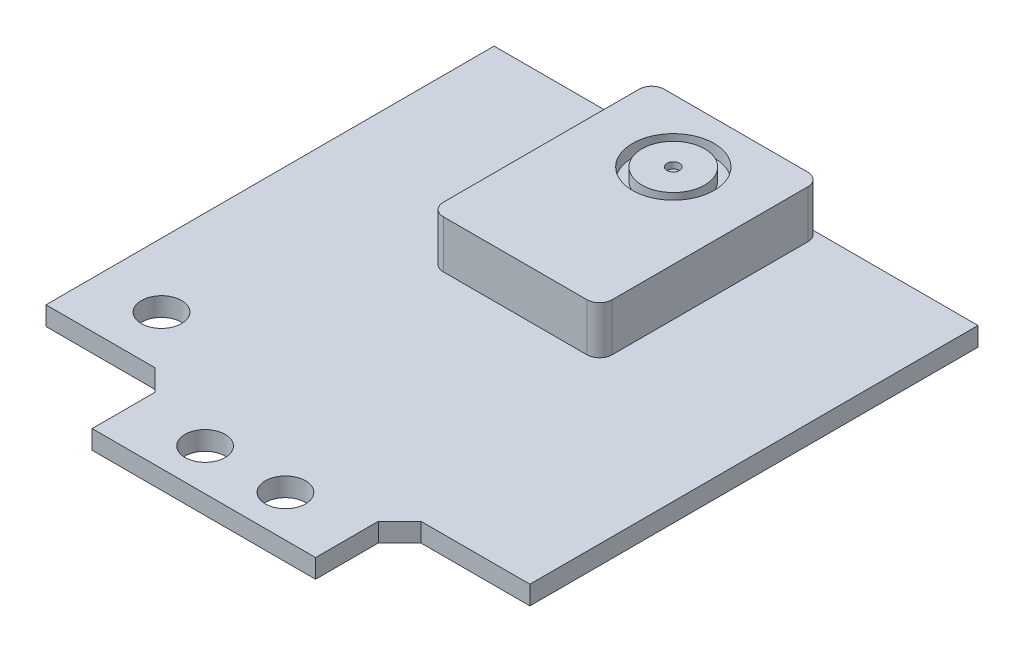
SolidWorks part; units mm, degrees
ref_plane "Front" through (0, 0, 0) normal (0, 0, 1) x (1, 0, 0)
ref_plane "Top" through (0, 0, 0) normal (0, 1, 0) x (1, 0, 0)
ref_plane "Right" through (0, 0, 0) normal (1, 0, 0) x (0, 0, -1)
sketch "Эскиз1" plane through (0, 0, 0) normal (0, 1, 0) x (1, 0, 0)
  line L0 (0, 36.5404) -> (0, -40.7648) construction
  line L1 (-19.275, 17.85) -> (19.275, 17.85)
  line L2 (-19.275, 17.85) -> (-19.275, -17.85)
  line L3 (-19.275, -17.85) -> (19.275, -17.85) construction
  line L4 (19.275, 17.85) -> (19.275, -17.85)
  line L5 (0, -17.85) -> (0, 17.85) construction
  line L6 (-19.275, 0) -> (19.275, 0) construction
  line L7 (-38.3655, 0) -> (47.2463, 0) construction
  line L8 (-19.275, -17.85) -> (-10.6, -17.85)
  line L9 (-10.6, -17.85) -> (-8.9, -19.55)
  line L10 (-8.9, -19.55) -> (-8.9, -24.55)
  line L11 (-8.9, -24.55) -> (8.9, -24.55)
  line L12 (19.275, -17.85) -> (10.6, -17.85)
  line L13 (10.6, -17.85) -> (8.9, -19.55)
  line L14 (8.9, -19.55) -> (8.9, -24.55)
  line L15 (-95.7643, 31.4517) -> (-103.5322, 31.4517)
  line L16 (5.725, 0.25) -> (-5.725, 0.25)
  line L17 (6.725, 1.25) -> (6.725, 16.85)
  line L18 (5.725, 17.85) -> (-5.725, 17.85)
  line L19 (-6.725, 1.25) -> (-6.725, 16.85)
  line L20 (6.725, 0.25) -> (-6.725, 17.85) construction
  line L21 (6.725, 17.85) -> (-6.725, 0.25) construction
  line L22 (-96.1644, -10.4583) -> (-103.0937, -10.4583)
  line L23 (-70.989, -10.2424) -> (-83.5848, -10.2424)
  line L24 (-87.1221, -3.4067) -> (-77.9203, -3.4067)
  circle A0 centre (-14.175, -13.75) radius 1.6
  circle A1 centre (-3.2, -21.25) radius 1.6
  circle A2 centre (3.2, -21.25) radius 1.6
  circle A3 centre (0, 12.85) radius 3.25
  arc A4 (6.725, 16.85) -> (5.725, 17.85) centre (5.725, 16.85) ccw
  arc A5 (-5.725, 17.85) -> (-6.725, 16.85) centre (-5.725, 16.85) ccw
  arc A6 (-5.725, 0.25) -> (-6.725, 1.25) centre (-5.725, 1.25) cw
  arc A7 (5.725, 0.25) -> (6.725, 1.25) centre (5.725, 1.25) ccw
  circle A8 centre (0, 12.85) radius 2.5
  point P8 (0, 12.85)
  point P22 (0, 9.05)
  point P48 (-45.1412, 35.0545)
  point P49 (-45.1412, -3.4067)
  point P50 (-56.4367, -10.2424)
  point P51 (-87.1221, 35.0545)
  point P320 (0, 0)
  dimension "D7" = 3.2
  dimension "D15" = 6.5
  dimension "D16" = 1
  dimension "D22" = 5
  dimension "D1" = 38.55
  dimension "D2" = 35.7
  dimension "D3" = 5
  dimension "D4" = 17.8
  dimension "D5" = 45
  dimension "D6" = 5
  dimension "D8" = 3.3
  dimension "D9" = 5.7
  dimension "D10" = 5.1
  dimension "D11" = 4.1
  dimension "D12" = 6.7
  dimension "D13" = 13.45
  dimension "D14" = 17.6
  dimension "D17" = 41.91
  dimension "D18" = 6.8357
  dimension "D19" = 41.981
  dimension "D20" = 38.4612
  dimension "D21" = 45.2969
extrude "Бобышка-Вытянуть1" add sketch "Эскиз1" along normal blind 1.5 contours A0 | A1 | A2 | L2 L8 L9 L10 L11 L14 L13 L12 L4 L1 region at (-14.175, 0, 13.75) region at (-3.2, 0, 21.25) region at (3.2, 0, 21.25)
extrude "Бобышка-Вытянуть2" add sketch "Эскиз1<3>" along normal blind 3.8 from surface separate body contours L19 A5 L18 A4 L17 A7 L16 A6 starting at face at (3.2, 1.5, 22.85)
sketch "Эскиз1<3>" plane through (0, 0, 0) normal (0, 1, 0) x (1, 0, 0) same geometry as "Эскиз1"
extrude "Вырез-Вытянуть1" cut sketch "Эскиз1<4>" against normal blind 1 from surface contours A8 | A3 region at (0, 0, -12.85) starting at face at (0, 5.3, -9.05)
sketch "Эскиз1<4>" plane through (0, 0, 0) normal (0, 1, 0) x (1, 0, 0) same geometry as "Эскиз1"
sketch "Эскиз2" plane through (0, 5.3, 0) normal (0, 1, 0) x (1, 0, 0)
  circle A0 centre (0, 12.85) radius 0.5
  dimension "D1" = 1
extrude "Вырез-Вытянуть2" cut sketch "Эскиз2" against normal blind 0.5
